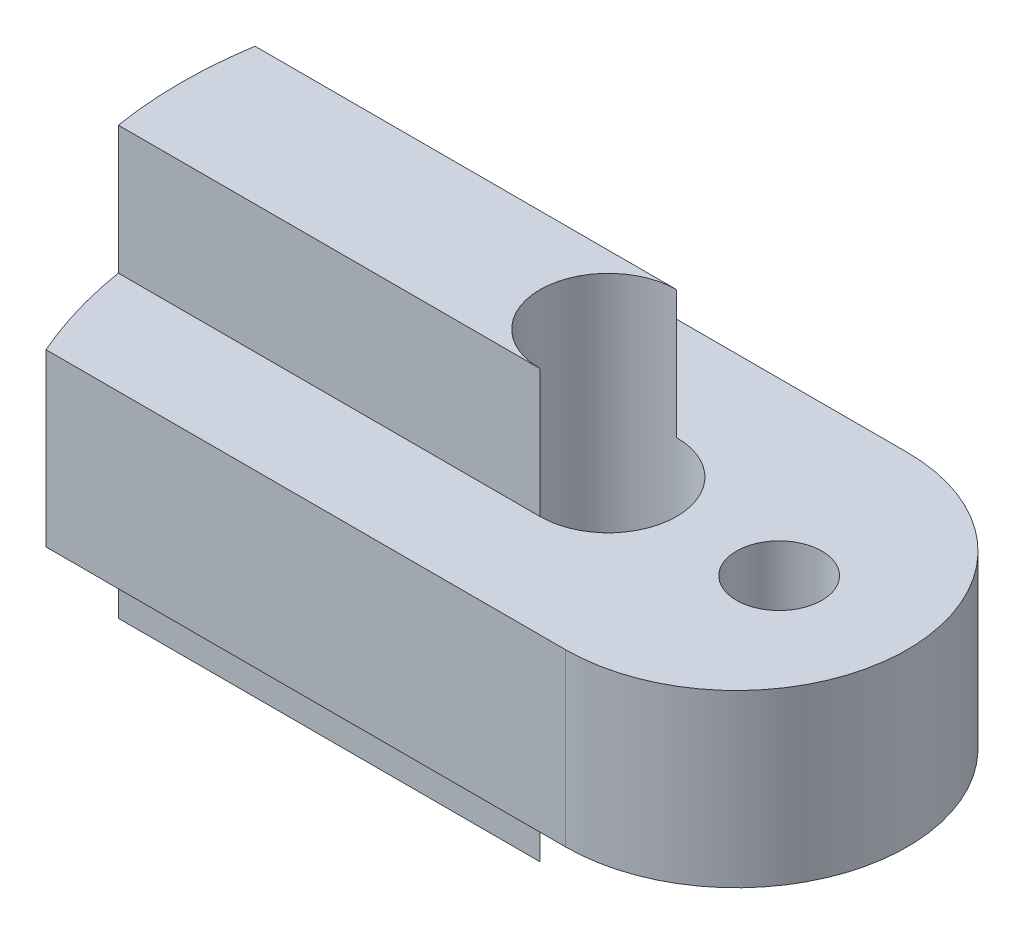
SolidWorks part; units mm, degrees
material "ABS"
ref_plane "Front Plane" through (0, 0, 0) normal (0, 0, 1) x (1, 0, 0)
ref_plane "Top Plane" through (0, 0, 0) normal (0, 1, 0) x (1, 0, 0)
ref_plane "Right Plane" through (0, 0, 0) normal (1, 0, 0) x (0, 0, -1)
sketch "Sketch2" plane through (0, 0, 0) normal (0, 1, 0) x (1, 0, 0)
  line L0 (0, -1.6) -> (-9.8712, -1.6)
  line L1 (0, 1.6) -> (-9.8712, 1.6)
  arc A0 (-9.8712, 1.6) -> (-9.8712, -1.6) centre (0, 0) ccw
  arc A1 (0, -1.6) -> (0, 1.6) centre (0, 0) ccw
  dimension "D1" = 20
  dimension "D2" = 3.2
extrude "Boss-Extrude3" add sketch "Sketch2" along normal blind 10
ref_point "Point2"
ref_axis "Axis1" through (0, -5.0031, 0) along (0, 1, 0)
ref_plane "Plane1" through (0, 5, 0) normal (0, 1, 0) x (1, 0, 0)
ref_point "Point3"
sketch "Sketch3" plane through (0, 5, 0) normal (0, 1, 0) x (1, 0, 0)
  line L0 (-10, 0) -> (3, 0)
  line L1 (-5.5, 0) -> (5.5, 0) construction
  line L2 (3, -4) -> (-9.1652, -4)
  line L3 (3, 4) -> (-9.1652, 4)
  arc A0 (-9.1652, 4) -> (-9.1652, -4) centre (0, 0) ccw
  arc A1 (3, -4) -> (3, 4) centre (3, 0) ccw
  dimension "D1" = 20
  dimension "D3" = 8
  dimension "D2" = 13
extrude "Boss-Extrude5" add sketch "Sketch3" along normal blind 2 and the other way blind 2 contours A1 L3 A0 L2
sketch "Sketch4" plane through (0, 10, 0) normal (0, 1, 0) x (1, 0, 0)
  circle A0 centre (0, 0) radius 1.6
extrude "Cut-Extrude1" cut sketch "Sketch4" against normal through all
sketch "Sketch5" plane through (0, 7, 0) normal (0, 1, 0) x (1, 0, 0)
  line L0 (-5.5, 0) -> (5.5, 0) construction
  circle A0 centre (4, 0) radius 1
  dimension "D1" = 4
  dimension "D2" = 2
extrude "Cut-Extrude3" cut sketch "Sketch5" against normal through all
